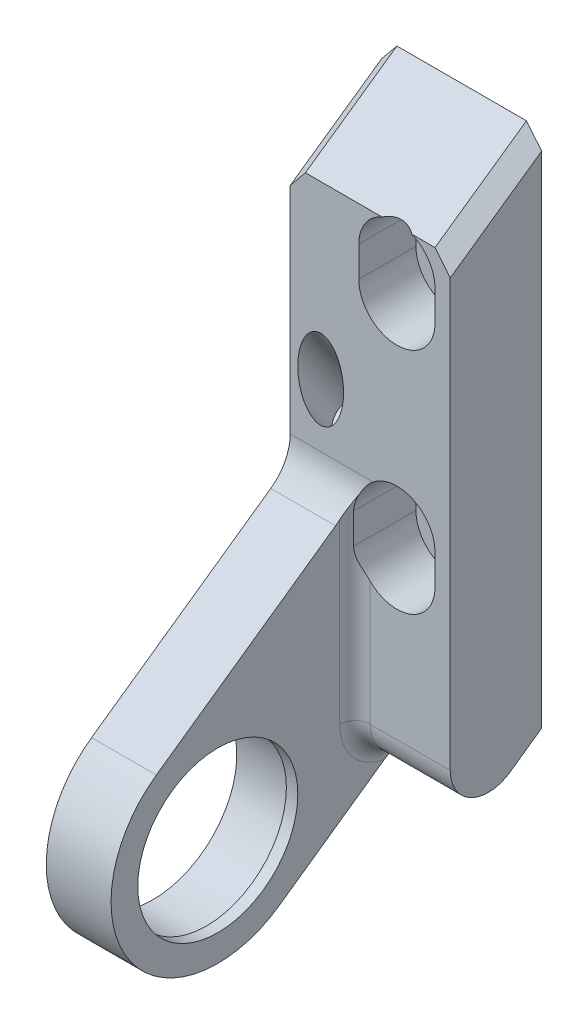
SolidWorks part; units mm, degrees
material "3D printed plastic"
ref_plane "Front Plane" through (0, 0, 0) normal (0, 0, 1) x (1, 0, 0)
ref_plane "Top Plane" through (0, 0, 0) normal (0, 1, 0) x (1, 0, 0)
ref_plane "Right Plane" through (0, 0, 0) normal (1, 0, 0) x (0, 0, -1)
sketch "Sketch1" plane through (0, 0, 0) normal (1, 0, 0) x (0, 0, -1)
  line L0 (30, 72) -> (30, 4)
  line L1 (8.0596, -11.4474) -> (30, 4)
  line L2 (18, 63.5975) -> (18, 29.795)
  line L4 (18, 29.795) -> (-8.0596, 11.4474)
  line L5 (30, 72) -> (18, 63.5975)
  circle A0 centre (0, 0) radius 10.5
  arc A1 (-8.0596, 11.4474) -> (8.0596, -11.4474) centre (0, 0) ccw
  dimension "D1" = 30
  dimension "D2" = 21
  dimension "D4" = 4
  dimension "D7" = 14
  dimension "D3" = 68
  dimension "D6" = 12
  dimension "D8" = 55
extrude "Boss-Extrude1" add sketch "Sketch1" along normal mid plane 21
sketch "Sketch2" plane through (0, 0, -18) normal (0, 0, 1) x (1, 0, 0)
  line L0 (3.5, 59) -> (3.5, 55) construction
  line L1 (5.75, 59) -> (5.75, 55)
  line L2 (1.25, 59) -> (1.25, 55)
  line L3 (3.5, 29) -> (3.5, 25) construction
  line L4 (5.75, 29) -> (5.75, 25)
  line L5 (1.25, 29) -> (1.25, 25)
  line L6 (3.5, 27) -> (3.5, 57) construction
  line L7 (3.5, 57) -> (3.5, 72) construction
  line L8 (10.5, 72) -> (-10.5, 72) construction
  line L10 (10.5, 72) -> (10.5, 63.5975) construction
  arc A0 (5.75, 59) -> (1.25, 59) centre (3.5, 59) ccw
  arc A1 (1.25, 55) -> (5.75, 55) centre (3.5, 55) ccw
  arc A2 (5.75, 29) -> (1.25, 29) centre (3.5, 29) ccw
  arc A3 (1.25, 25) -> (5.75, 25) centre (3.5, 25) ccw
  point P2 (3.5, 57)
  point P7 (3.5, 27)
  dimension "D1" = 30
  dimension "D2" = 4
  dimension "D3" = 4.5
  dimension "D4" = 15
  dimension "D5" = 7
extrude "Cut-Extrude1" cut sketch "Sketch2" against normal through all both and the other way through all
sketch "Sketch3" plane through (0, 0, -18) normal (0, 0, 1) x (1, 0, 0)
  line L0 (3.5, 59) -> (3.5, 55) construction
  line L1 (8.5, 59) -> (8.5, 55)
  line L2 (-1.5, 59) -> (-1.5, 55)
  line L3 (3.5, 29) -> (3.5, 25) construction
  line L4 (8.5, 29) -> (8.5, 25)
  line L5 (-1.5, 29) -> (-1.5, 25)
  arc A0 (8.5, 59) -> (-1.5, 59) centre (3.5, 59) ccw
  arc A1 (-1.5, 55) -> (8.5, 55) centre (3.5, 55) ccw
  arc A2 (8.5, 29) -> (-1.5, 29) centre (3.5, 29) ccw
  arc A3 (-1.5, 25) -> (8.5, 25) centre (3.5, 25) ccw
  point P4 (3.5, 57)
  point P9 (3.5, 27)
  dimension "D1" = 10
extrude "Cut-Extrude2" cut sketch "Sketch3" against normal blind 7.5 and the other way through all
sketch "Sketch4" plane through (-10.5, 0, 0) normal (-1, 0, 0) x (0, 0, 1)
  circle A0 centre (0, 0) radius 11
  dimension "D1" = 22
extrude "Cut-Extrude3" cut sketch "Sketch4" against normal blind 7
sketch "Sketch5" plane through (10.5, 0, 0) normal (1, 0, 0) x (0, 0, -1)
  line L0 (18, 29.795) -> (18, 24)
  line L1 (18, 29.795) -> (3.619, 19.6698)
  line L2 (18, 29.795) -> (-8.0596, 11.4474) construction
  line L3 (18, 24) -> (18, -4.4487)
  line L4 (8.0596, -11.4474) -> (30, 4) construction
  line L5 (18, -4.4487) -> (18, -8.7178)
  arc A0 (3.619, 19.6698) -> (18, -8.7178) centre (0, 0) ccw
  dimension "D1" = 40
extrude "Cut-Extrude4" cut sketch "Sketch5" against normal offset from surface (12.5 mm away) 8.5 up to face at (-10.5, 0, 11)
chamfer "Chamfer1" distance 2 angle 45 2 edges at (-10.5, 67.7988, -24) (10.5, 67.7988, -24)
ref_plane "Plane1" through (-6.5, 0, 0) normal (-1, 0, 0) x (0, 0, 1)
sketch "Sketch6" plane through (-6.5, 0, 0) normal (-1, 0, 0) x (0, 0, 1)
  line L0 (-30, 24) -> (-16.6484, 43.0681) construction
  line L1 (-30, 4) -> (-30, 69.5585) construction
  line L2 (-30, 24) -> (-31.3516, 22.0697) construction
  line L3 (-31.3516, 22.0697) -> (-30, 21.1233)
  line L4 (-30, 21.1233) -> (-15.2968, 42.1217)
  line L5 (-15.2968, 42.1217) -> (-16.6484, 43.0681)
  line L6 (-16.6484, 43.0681) -> (-18, 44.0145) construction
  line L7 (-18, 61.156) -> (-18, 29.795) construction
  line L8 (-16.6484, 43.0681) -> (-31.3516, 22.0697)
  dimension "D1" = 3.3
  dimension "D2" = 35
  dimension "D3" = 20
revolve "Cut-Revolve1" cut sketch "Sketch6" angle 360 about L8
ref_plane "Plane2" through (-6.5, 22.0697, -31.3516) normal (0, -0.8192, -0.5736) x (-1, 0, 0)
sketch "Sketch7" plane through (-6.5, 22.0697, -31.3516) normal (0, -0.8192, -0.5736) x (-1, 0, 0)
  line L1 (0, -3.1754) -> (2.75, -1.5877)
  line L2 (2.75, -1.5877) -> (2.75, 1.5877)
  line L3 (2.75, 1.5877) -> (0, 3.1754)
  line L4 (0, 3.1754) -> (-2.75, 1.5877)
  line L5 (-2.75, 1.5877) -> (-2.75, -1.5877)
  line L6 (-2.75, -1.5877) -> (0, -3.1754)
  circle A0 centre (0, 0) radius 2.75 construction
  dimension "D1" = 5.5
extrude "Cut-Extrude5" cut sketch "Sketch7" against normal blind 9 and the other way through all
sketch "Sketch8" plane through (0, 7.4509, 5.2172) normal (0, -0.8192, -0.5736) x (1, 0, 0)
  circle A0 centre (-6.5, -38.3404) radius 3
  dimension "D1" = 6
extrude "Cut-Extrude6" cut sketch "Sketch8" against normal through all from offset 5 offset against normal yes
fillet "Fillet5" radius 5 1 edges at (4.25, -4.4487, -18)
fillet "Fillet1" radius 2 2 edges at (-2, 17.4907, -18) (-2, 0.7485, -20.697)
fillet "Fillet3" radius 6 1 edges at (-5.9682, 29.795, -18)
